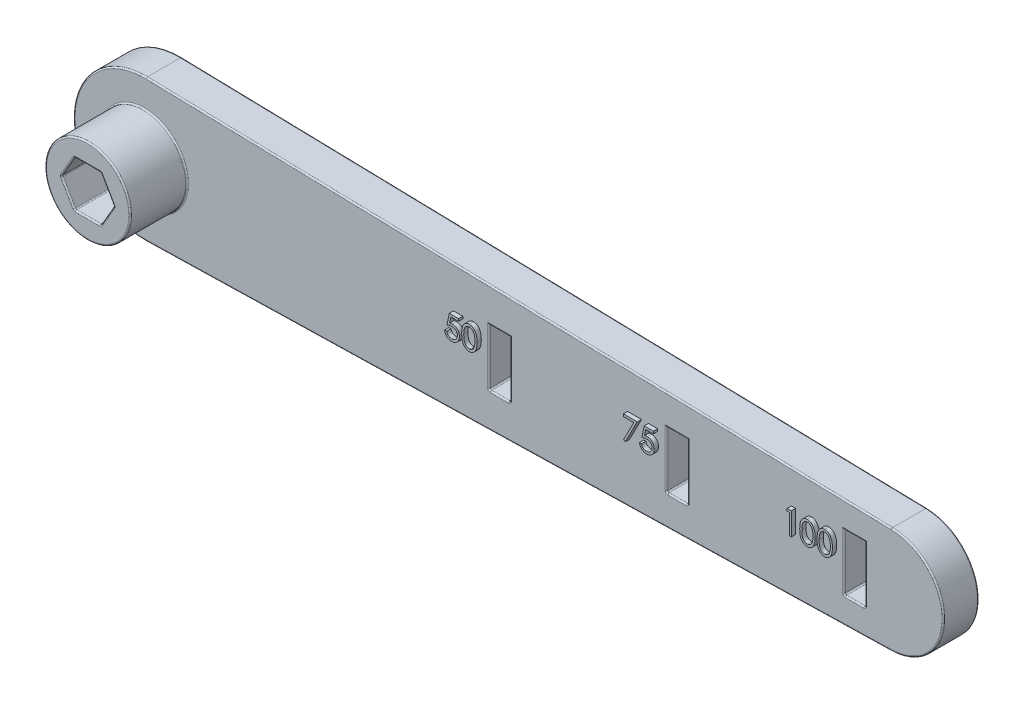
SolidWorks part; units mm, degrees
ref_plane "Front Plane" through (0, 0, 0) normal (0, 0, 1) x (1, 0, 0)
ref_plane "Top Plane" through (0, 0, 0) normal (0, 1, 0) x (1, 0, 0)
ref_plane "Right Plane" through (0, 0, 0) normal (1, 0, 0) x (0, 0, -1)
sketch "Sketch3" plane through (0, 0, 0) normal (0, 0, 1) x (1, 0, 0)
  line L0 (0.2381, 9.9972) -> (105.1786, 7.4979)
  line L1 (105.1786, -7.4979) -> (0.2381, -9.9972)
  arc A0 (0.2381, 9.9972) -> (0.2381, -9.9972) centre (0, 0) ccw
  arc A1 (105.1786, -7.4979) -> (105.1786, 7.4979) centre (105, 0) ccw
  dimension "D1" = 20
  dimension "D2" = 15
  dimension "D3" = 105
extrude "Boss-Extrude1" add sketch "Sketch3" along normal blind 5
sketch "Sketch2" plane through (0, 0, 0) normal (0, 0, 1) x (1, 0, 0)
  line L2 (3.695, 0) -> (1.8475, 3.2)
  line L3 (1.8475, 3.2) -> (-1.8475, 3.2)
  line L4 (-1.8475, 3.2) -> (-3.695, 0)
  line L5 (-3.695, 0) -> (-1.8475, -3.2)
  line L6 (-1.8475, -3.2) -> (1.8475, -3.2)
  line L7 (1.8475, -3.2) -> (3.695, 0)
  circle A1 centre (0, 0) radius 3.2 construction
  dimension "D1" = 6.4
extrude "Cut-Extrude2" cut sketch "Sketch2" along normal up to next
sketch "Sketch4" plane through (0, 0, 5) normal (0, 0, 1) x (1, 0, 0)
  line L1 (98.5, 4) -> (101.5, 4)
  line L2 (98.5, 4) -> (98.5, -4)
  line L3 (98.5, -4) -> (101.5, -4)
  line L4 (101.5, 4) -> (101.5, -4)
  line L5 (100, -4) -> (100, 4) construction
  line L6 (0, 0) -> (112.5, 0) construction
  line L7 (73.5, 4) -> (76.5, 4)
  line L8 (73.5, 4) -> (73.5, -4)
  line L9 (73.5, -4) -> (76.5, -4)
  line L10 (76.5, 4) -> (76.5, -4)
  line L11 (75, -4) -> (75, 4) construction
  line L12 (48.5, 4) -> (51.5, 4)
  line L13 (48.5, 4) -> (48.5, -4)
  line L14 (48.5, -4) -> (51.5, -4)
  line L15 (51.5, 4) -> (51.5, -4)
  line L16 (50, -4) -> (50, 4) construction
  arc A0 (105.1786, -7.4979) -> (105.1786, 7.4979) centre (105, 0) ccw construction
  point P4 (100, 0)
  point P33 (50, 0)
  point P34 (75, 0)
  dimension "D1" = 8
  dimension "D3" = 3
  dimension "D4" = 50
  dimension "D5" = 75
  dimension "D6" = 100
extrude "Cut-Extrude3" cut sketch "Sketch4" against normal up to next
sketch "Sketch6" plane through (0, 0, 5) normal (0, 0, 1) x (1, 0, 0)
  line L1 (3.695, 0) -> (1.8475, 3.2) construction
  line L2 (3.695, 0) -> (1.8475, 3.2)
  line L3 (1.8475, 3.2) -> (-1.8475, 3.2)
  line L4 (-1.8475, 3.2) -> (-3.695, 0)
  line L5 (-3.695, 0) -> (-1.8475, -3.2)
  line L6 (-1.8475, -3.2) -> (1.8475, -3.2)
  line L7 (1.8475, -3.2) -> (3.695, 0)
  circle A0 centre (0, 0) radius 6
  circle A2 centre (0, 0) radius 3.2 construction
  dimension "D1" = 12
extrude "Boss-Extrude3" add sketch "Sketch6" along normal blind 8
fillet "Fillet1" radius 0.2 58 edges at (51.5, -4, 2.5) (48.5, -4, 2.5) (101.5, -4, 2.5) (98.5, -4, 2.5) (76.5, -4, 2.5) (73.5, -4, 2.5) (76.5, 0, 0) (75, -4, 0) (73.5, 0, 0) (52.7083, 8.7475, 0) (51.5, 0, 0) (50, -4, 0) (48.5, 0, 0) (-10, 0, 0) (52.7083, -8.7475, 0) (112.5, 0, 0) (101.5, 0, 0) (100, -4, 0) (98.5, 0, 0) (100, -4, 5) (101.5, 0, 5) (52.7083, 8.7475, 5) (112.5, 0, 5) (52.7083, -8.7475, 5) (-10, 0, 5) (48.5, 0, 5) (50, -4, 5) (51.5, 0, 5) (73.5, 0, 5) (75, -4, 5) (76.5, 0, 5) (98.5, 0, 5) (6, 0, 5) (6, 0, 13) (50, 4, 0) (75, 4, 0) (100, 4, 0) (100, 4, 5) (75, 4, 5) (50, 4, 5) (0, -3.2, 0) (-2.7713, -1.6, 0) (-2.7713, 1.6, 0) (0, 3.2, 0) (2.7713, 1.6, 0) (2.7713, -1.6, 0) (2.7713, 1.6, 13) (0, -3.2, 13) (-2.7713, 1.6, 13) (3.695, 0, 6.5) (2.7713, -1.6, 13) (1.8475, -3.2, 6.5) (-1.8475, 3.2, 6.5) (0, 3.2, 13) (1.8475, 3.2, 6.5) (-1.8475, -3.2, 6.5) (-2.7713, -1.6, 13) (-3.695, 0, 6.5)
sketch "Sketch5" plane through (0, 0, 5) normal (0, 0, 1) x (1, 0, 0)
  line L0 (0, 0) -> (112.3, 0) construction
  line L1 (48.5, 4) -> (48.5, -3.8) construction
  line L2 (73.5, 4) -> (73.5, -3.8) construction
  line L3 (98.5, 4) -> (98.5, -3.8) construction
  arc A0 (105.1738, -7.2979) -> (105.1738, 7.2979) centre (105, 0) ccw construction
  text T0 "50"
  text T1 "75"
  text T2 "100"
  dimension "D1" = 5.8
  dimension "D2" = 5.8
  dimension "D3" = 8.2
extrude "Boss-Extrude2" add sketch "Sketch5" along normal blind 0.6
